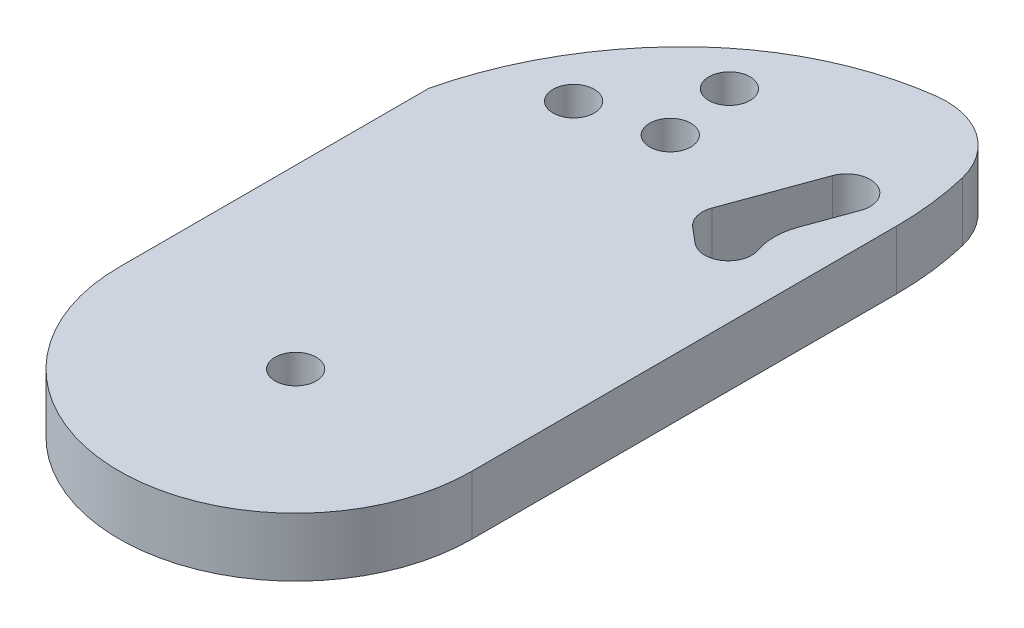
SolidWorks part; units mm, degrees
ref_plane "Front Plane" through (0, 0, 0) normal (0, 0, 1) x (1, 0, 0)
ref_plane "Top Plane" through (0, 0, 0) normal (0, 1, 0) x (1, 0, 0)
ref_plane "Right Plane" through (0, 0, 0) normal (1, 0, 0) x (0, 0, -1)
sketch "Sketch1" plane through (0, 0, 0) normal (0, 1, 0) x (1, 0, 0)
  line L0 (0, 0) -> (0, 50) construction
  line L1 (-15, 0) -> (-15, 50)
  line L2 (15, 0) -> (15, 50)
  line L3 (10.4451, 36.3547) -> (7.709, 28.8372) construction
  line L4 (12.3245, 35.6707) -> (10.0673, 29.4691)
  line L5 (8.5657, 37.0388) -> (5.8296, 29.5212)
  line L6 (0, 65) -> (0, 60) construction
  line L7 (0, 60) -> (-6.5, 48.7417) construction
  line L8 (-6.5, 48.7417) -> (6.5, 48.7417) construction
  line L9 (6.5, 48.7417) -> (0, 60) construction
  line L10 (7.709, 28.8372) -> (9, 27.7539) construction
  line L11 (10.0673, 29.4691) -> (10.2856, 29.286)
  line L12 (6.4234, 27.3051) -> (7.7144, 26.2218)
  arc A0 (-15, 0) -> (15, 0) centre (0, 0) ccw
  arc A1 (15, 50) -> (-15, 50) centre (0, 50) ccw
  circle A2 centre (0, 0) radius 1.75
  arc A3 (12.3245, 35.6707) -> (8.5657, 37.0388) centre (10.4451, 36.3547) ccw
  arc A4 (5.8296, 29.5212) -> (6.4234, 27.3051) centre (7.709, 28.8372) ccw
  circle A5 centre (0, 60) radius 3.175 construction
  circle A6 centre (-6.5, 48.7417) radius 3.175 construction
  circle A7 centre (6.5, 48.7417) radius 3.175 construction
  arc A9 (5.8296, 29.5212) -> (6.4234, 27.3051) centre (7.709, 28.8372) ccw
  arc A10 (7.7144, 26.2218) -> (10.2856, 29.286) centre (9, 27.7539) ccw
  point P3 (0, 25)
  point P12 (6.2189, 27.2917)
  point P24 (5.4964, 12.8256)
  dimension "D1" = 15
  dimension "D2" = 3.5
  dimension "D4" = 2
  dimension "D7" = 6.35
  dimension "D8" = 5
  dimension "D12" = 110
  dimension "D3" = 50
  dimension "D5" = 20
  dimension "D6" = 8
  dimension "D9" = 13
  dimension "D10" = 13
  dimension "D11" = 6
  dimension "D13" = 13.6453
extrude "Boss-Extrude1" add sketch "Sketch1" along normal blind 5 contours L2 A1 L1 A0 A10 L12 A4 L5 A3 L4 L11 A7 A6 A5 A2 region at (-0.2169, 0, -24.9479)
fillet "Fillet1" radius 5 1 edges at (10.0673, 2.5, -29.4691)
sketch "Sketch2" plane through (0, 5, 0) normal (0, 1, 0) x (1, 0, 0)
  line L0 (15, 0) -> (15, 50) construction
  line L2 (-15, 0) -> (-15, 50) construction
  line L3 (-15, 26.3246) -> (-40.9256, 69.2382)
  line L4 (-40.9256, 69.2382) -> (-58.772, 111.0807)
  line L5 (-58.772, 111.0807) -> (39.2844, 102.8258)
  line L6 (39.2844, 102.8258) -> (15, 36.047)
  arc A0 (15, 36.047) -> (14.2432, 42.3998) centre (-12.0434, 36.047) ccw
  arc A1 (14.2432, 42.3998) -> (7.1271, 47.2922) centre (7.9593, 40.8811) ccw
  arc A2 (7.1271, 47.2922) -> (-6.484, 40.9149) centre (10.3077, 22.7899) ccw
  arc A3 (-6.484, 40.9149) -> (-15, 26.3246) centre (13.2458, 19.6186) ccw
extrude "Cut-Extrude1" cut sketch "Sketch2" against normal blind 10
sketch "Sketch3" plane through (0, 5, 0) normal (0, 1, 0) x (1, 0, 0)
  circle A0 centre (6.1014, 47.3659) radius 3.81 construction
  circle A1 centre (-1.3018, 33.1261) radius 1.75
  circle A2 centre (3.3822, 36.8758) radius 1.75 construction
  circle A3 centre (-2.2071, 39.0574) radius 1.75
  circle A4 centre (-7.9059, 31.5198) radius 1.75
  dimension "D1" = 7.62
  dimension "D2" = 3.5
  dimension "D7" = 3.5
  dimension "D3" = 10
  dimension "D4" = 6
  dimension "D5" = 6
  dimension "D6" = 6
extrude "Cut-Extrude2" cut sketch "Sketch3" against normal blind 10
